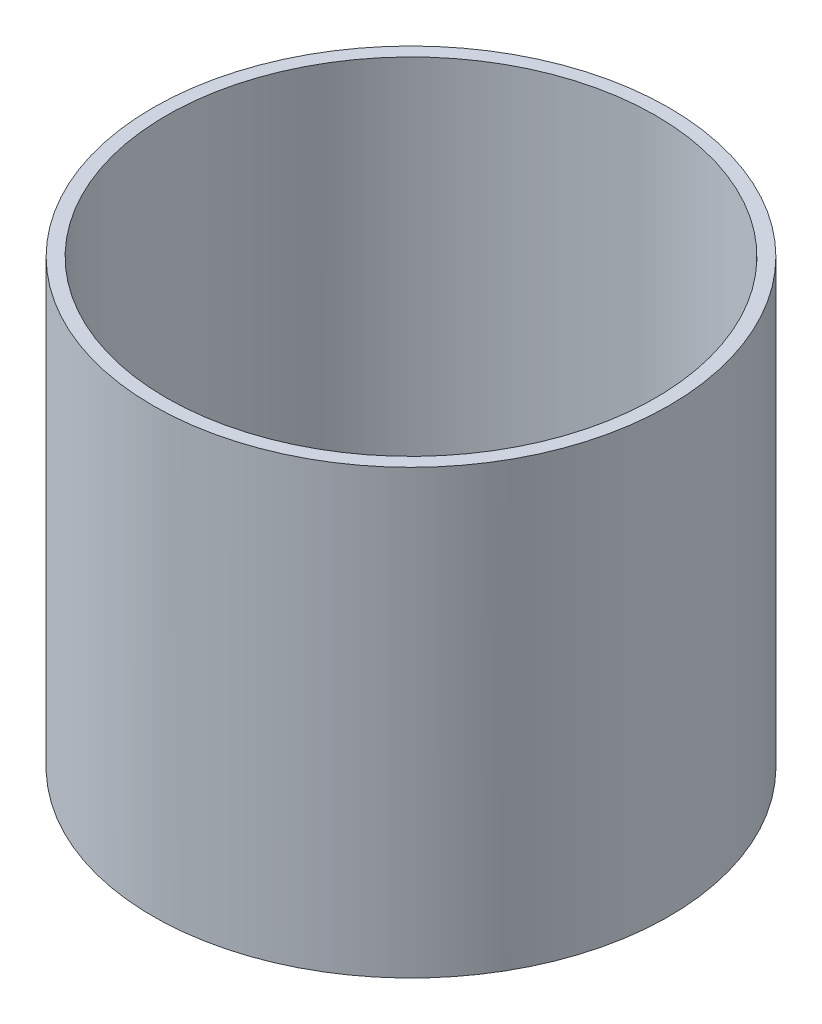
SolidWorks part; units mm, degrees
ref_plane "Спереди" through (0, 0, 0) normal (0, 0, 1) x (1, 0, 0)
ref_plane "Сверху" through (0, 0, 0) normal (0, 1, 0) x (1, 0, 0)
ref_plane "Справа" through (0, 0, 0) normal (1, 0, 0) x (0, 0, -1)
sketch "Эскиз1" plane through (0, 0, 0) normal (0, 1, 0) x (1, 0, 0)
  circle A0 centre (0, 0) radius 36.5
  circle A1 centre (0, 0) radius 38.5
  dimension "D1" = 73
  dimension "D2" = 2
extrude "Бобышка-Вытянуть1" add sketch "Эскиз1" along normal blind 73
ref_plane "Плоскость1" through (0, 0, 36.5) normal (0, 0, 1) x (1, 0, 0)
sketch "Эскиз2" plane through (0, 0, 36.5) normal (0, 0, 1) x (1, 0, 0)
  line L1 (1.95, 20.4471) -> (-0.95, 20.4471)
  line L2 (1.95, 20.4471) -> (1.95, 9)
  line L3 (1.95, 9) -> (-2.05, 9)
  line L4 (-2.05, 20.4471) -> (-2.05, 9)
  line L9 (-0.95, 20.4471) -> (-2.05, 20.4471)
  line L10 (-36.5, 0) -> (36.5, 0) construction
  point P0 (0, 15.7235)
  dimension "D1" = 4
  dimension "D2" = 11.4471
  dimension "D5" = 9
extrude "Бобышка-Вытянуть3" add sketch "Эскиз2" against normal blind 1.6
pattern_circular "Круговой массив1" count 3 over 360 about axis through (0, 73, 0) along (0, -1, 0) of "Бобышка-Вытянуть3"
sketch "Эскиз3" plane through (0, 0, 0) normal (0, -1, 0) x (1, 0, 0)
  circle A0 centre (0, 0) radius 52.9278
extrude "Вырез-Вытянуть1" cut sketch "Эскиз3" against normal blind 7
